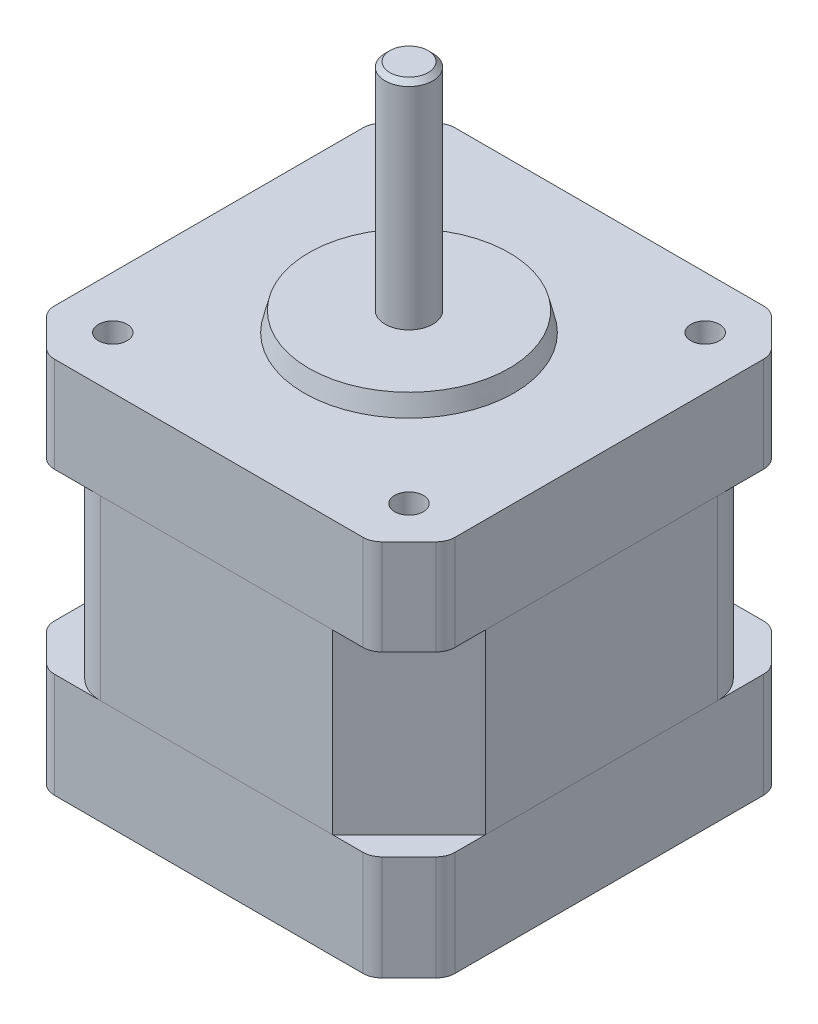
SolidWorks part; units mm, degrees
ref_plane "Front Plane" through (0, 0, 0) normal (0, 0, 1) x (1, 0, 0)
ref_plane "Top Plane" through (0, 0, 0) normal (0, 1, 0) x (1, 0, 0)
ref_plane "Right Plane" through (0, 0, 0) normal (1, 0, 0) x (0, 0, -1)
sketch "Sketch1" plane through (0, 0, 0) normal (0, 1, 0) x (1, 0, 0)
  line L1 (-21, 21) -> (21, 21)
  line L2 (-21, 21) -> (-21, -21)
  line L3 (-21, -21) -> (21, -21)
  line L4 (21, 21) -> (21, -21)
  dimension "D1" = 42
  dimension "D2" = 42
extrude "Boss-Extrude1" add sketch "Sketch1" along normal blind 10
sketch "Sketch2" plane through (0, 10, 0) normal (0, 1, 0) x (1, 0, 0)
  circle A0 centre (0, 0) radius 11
  dimension "D1" = 22
extrude "Boss-Extrude2" add sketch "Sketch2" along normal blind 2
sketch "Sketch3" plane through (0, 12, 0) normal (0, 1, 0) x (1, 0, 0)
  circle A0 centre (0, 0) radius 2.5
  dimension "D1" = 5
extrude "Boss-Extrude3" add sketch "Sketch3" along normal blind 22.6
chamfer "Chamfer2" distance 0.5 angle 45 1 edges at (0, 34.6, 2.5)
chamfer "Chamfer3" distance 2 distance2 0.5 1 edges at (0, 12, 11) first distance on face at (0, 12, 11)
extrude "Boss-Extrude6" add sketch "Sketch1<4>" against normal blind 18.6 separate body
sketch "Sketch1<4>" plane through (0, 0, 0) normal (0, 1, 0) x (1, 0, 0) same geometry as "Sketch1"
sketch "Sketch6" plane through (0, -18.6, 0) normal (0, -1, 0) x (1, 0, 0)
  line L1 (-21, -21) -> (21, -21)
  line L2 (-21, -21) -> (-21, 21)
  line L3 (-21, 21) -> (21, 21)
  line L4 (21, -21) -> (21, 21)
extrude "Boss-Extrude7" add sketch "Sketch6" along normal blind 11 separate body
chamfer "Chamfer5" distance 4 angle 45 4 edges at (21, 5, -21) (21, 5, 21) (-21, 5, 21) (-21, 5, -21)
chamfer "Chamfer6" distance 4 angle 45 4 edges at (21, -24.1, -21) (-21, -24.1, -21) (-21, -24.1, 21) (21, -24.1, 21)
fillet "Fillet2" radius 2 8 edges at (17, 5, -21) (21, 5, -17) (21, 5, 17) (17, 5, 21) (-17, 5, 21) (-21, 5, 17) (-17, 5, -21) (-21, 5, -17)
fillet "Fillet3" radius 2 8 edges at (17, -24.1, -21) (21, -24.1, -17) (17, -24.1, 21) (21, -24.1, 17) (-17, -24.1, 21) (-21, -24.1, 17) (-17, -24.1, -21) (-21, -24.1, -17)
sketch "Sketch7" plane through (0, 0, -21) normal (0, 0, -1) x (-1, 0, 0)
  line L0 (16.1716, -18.6) -> (-16.1716, -18.6) construction
  line L1 (-4, -20.1) -> (4, -20.1)
  line L2 (-4, -20.1) -> (-4, -27.1)
  line L3 (-4, -27.1) -> (4, -27.1)
  line L4 (4, -20.1) -> (4, -27.1)
  line L6 (-21, -18.6) -> (21, -18.6) construction
  point P6 (0, -20.1)
  point P9 (0, -18.6)
  dimension "D1" = 8
  dimension "D2" = 7
  dimension "D3" = 1.5
  dimension "D4" = 0
extrude "Boss-Extrude8" add sketch "Sketch7" along normal blind 0.5
chamfer "Chamfer7" distance 8 angle 45 4 edges at (-21, -9.3, -21) (-21, -9.3, 21) (21, -9.3, 21) (21, -9.3, -21)
fillet "Fillet4" radius 4 6 edges at (-13, -9.3, 21) (-21, -9.3, 13) (-13, -9.3, -21) (-21, -9.3, -13) (13, -9.3, -21) (21, -9.3, -13)
sketch "Sketch8" plane through (0, 10, 0) normal (0, 1, 0) x (1, 0, 0)
  circle A0 centre (-15.525, 15.525) radius 1.5
  circle A1 centre (15.525, 15.525) radius 1.5
  circle A2 centre (15.525, -15.525) radius 1.5
  circle A3 centre (-15.525, -15.525) radius 1.5
  dimension "D1" = 3
  dimension "D2" = 31.05
  dimension "D3" = 31.05
  dimension "D4" = 15.525
  dimension "D5" = 15.525
extrude "Cut-Extrude2" cut sketch "Sketch8" against normal blind 15
